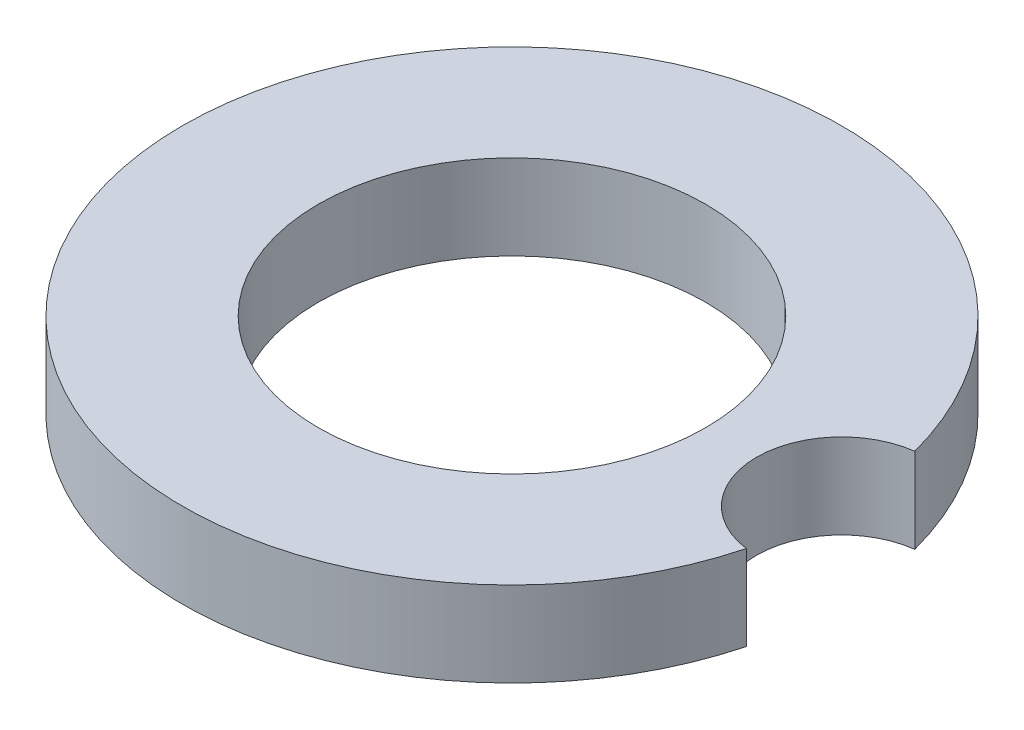
SolidWorks part; units mm, degrees
ref_plane "Front Plane" through (0, 0, 0) normal (0, 0, 1) x (1, 0, 0)
ref_plane "Top Plane" through (0, 0, 0) normal (0, 1, 0) x (1, 0, 0)
ref_plane "Right Plane" through (0, 0, 0) normal (1, 0, 0) x (0, 0, -1)
sketch "Sketch1" plane through (0, 0, 0) normal (0, 1, 0) x (1, 0, 0)
  circle A0 centre (0, 0) radius 28.9526
  circle A1 centre (0, 0) radius 49.276
  dimension "Front_CR_ID" = 57.9052
  dimension "Front_CR_OD" = 98.552
extrude "Boss-Extrude1" add sketch "Sketch1" along normal blind 12.7 contours A1
extrude "Cut-Extrude2" cut sketch "Sketch1<10>" along normal through all contours A0
sketch "Sketch1<10>" plane through (0, 0, 0) normal (0, 1, 0) x (1, 0, 0) same geometry as "Sketch1"
sketch "Sketch2" plane through (0, 12.7, 0) normal (0, 1, 0) x (1, 0, 0)
  circle A2 centre (49.276, 0) radius 12.7
  point P4 (49.276, 0)
  dimension "D1" = 25.4
  dimension "D2" = 49.276
extrude "Cut-Extrude3" cut sketch "Sketch2" against normal through all contours A2
ref_plane "Plane1" through (0, 6.35, 0) normal (0, -1, 0) x (-1, 0, 0)
equation "\"Motor_OD\" = 54.4mm"
equation "\"Aft_Section_Length\" = 32in"
equation "\"Mid_Coupler_Length\" = 12in"
equation "\"AB_Coupler_OD_Length\"= 1in"
equation "\"AB_Coupling_Section_Length\"= 0.375in"
equation "\"AB_Coupler_Length\"= \"AB_Coupler_OD_Length\" + \"AB_Coupling_Section_Length\" * 2"
equation "\"Cutout_Angle\" = 60"
equation "\"AB_Paddle_Height\" = 0.375in"
equation "\"AB_Coupler_Num_Screws\"= 4"
equation "\"Num_Cutouts\" = 4"
equation "\"AB_Coupler_OD\"= 4.024in"
equation "\"AB_Coupler_ID\"= 3.7in"
equation "\"AB_Coupler_Surface_Diameter\"= 3.899in"
equation "\"AB_Coupling_Screw_Diameter\"= 0.1065in"
equation "\"AB_Central_Bushing_Length\" = 0.75in"
equation "\"Lead_Screw_Dist\" = 2in"
equation "\"Lead_Screw_Diam\" = 0.375in"
equation "\"Lead_Screw_Length\" = \"Mid_Coupler_Length\" + 2*0.375in + 2*0.5in"
equation "\"Paddle_Pin_Offset\" = 0.25in"
equation "\"Paddle_Pin_Radius\" = 2.25*2/3in"
equation "\"Paddle_Gear_OD\" = 3.2in"
equation "\"Fwd_BKHD_From_Top\" = 18in"
equation "\"Front_CR_ID@Sketch1\" = \"Motor_OD\" + 0.118 + 0.02"
equation "\"Body_Tube_OD\"= 4.024in"
equation "\"Body_Tube_ID\"= 3.90in"
equation "\"Coupler_OD\" = 3.899in"
equation "\"Coupler_ID\" = 3.755in"
equation "\"Fwd_Section_Length\" = 20in"
equation "\"Mid_Section_Length\" = 4in"
equation "\"Aft_Upper_Tube_Length\" = 10in"
equation "\"Aft_Lower_Tube_Length\" = 18in"
equation "\"Nosecone_Coupler_Length\" = 5in"
equation "\"Avionics_Bulkhead_Thickness\" = 0.25in"
equation "\"Avionics_Bulkhead_Lip\" = 0.125in"
equation "\"Avionics_Board_Length\" = \"Mid_Coupler_Length\" - 2*\"Avionics_Bulkhead_Lip\""
equation "\"Lead_Screw_Hole_Diam\" = 0.386in"
equation "\"Front_CR_OD@Sketch1\"= \"Body_Tube_ID\" - 0.02"
equation "\"Centering_Ring_Cutout_Dia\"= 1in"
equation "\"D1@Sketch2\"=\"Centering_Ring_Cutout_Dia\""
